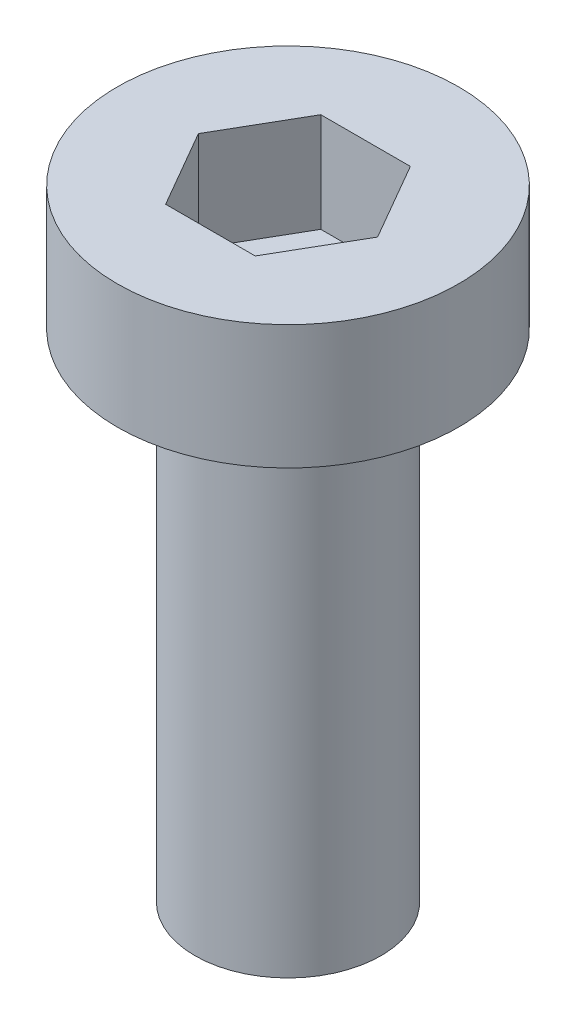
SolidWorks part; units mm, degrees
material "AISI 304"
ref_plane "前视基准面" through (0, 0, 0) normal (0, 0, 1) x (1, 0, 0)
ref_plane "上视基准面" through (0, 0, 0) normal (0, 1, 0) x (1, 0, 0)
ref_plane "右视基准面" through (0, 0, 0) normal (1, 0, 0) x (0, 0, -1)
sketch "草图1" plane through (0, 0, 0) normal (0, 1, 0) x (1, 0, 0)
  circle A0 centre (0, 0) radius 1.5
  circle A1 centre (0, 0) radius 2.75
  dimension "公称直径" = 3
  dimension "外径" = 5.5
extrude "头部高" add sketch "草图1" along normal blind 2 contours A0 | A1 A0 region at (0, 0, 0) region at (-2.6722, 0, 0)
extrude "公称长度" add sketch "草图1<3>" against normal blind 8 contours A0 region at (0, 0, 0)
sketch "草图1<3>" plane through (0, 0, 0) normal (0, 1, 0) x (1, 0, 0) same geometry as "草图1"
sketch "草图2" plane through (0, 2, 0) normal (0, 1, 0) x (1, 0, 0)
  line L1 (1.4434, 0) -> (0.7217, 1.25)
  line L2 (0.7217, 1.25) -> (-0.7217, 1.25)
  line L3 (-0.7217, 1.25) -> (-1.4434, 0)
  line L4 (-1.4434, 0) -> (-0.7217, -1.25)
  line L5 (-0.7217, -1.25) -> (0.7217, -1.25)
  line L6 (0.7217, -1.25) -> (1.4434, 0)
  circle A0 centre (0, 0) radius 1.25 construction
  dimension "D1" = 2.5
extrude "切除-拉伸1" cut sketch "草图2" against normal blind 1.6
